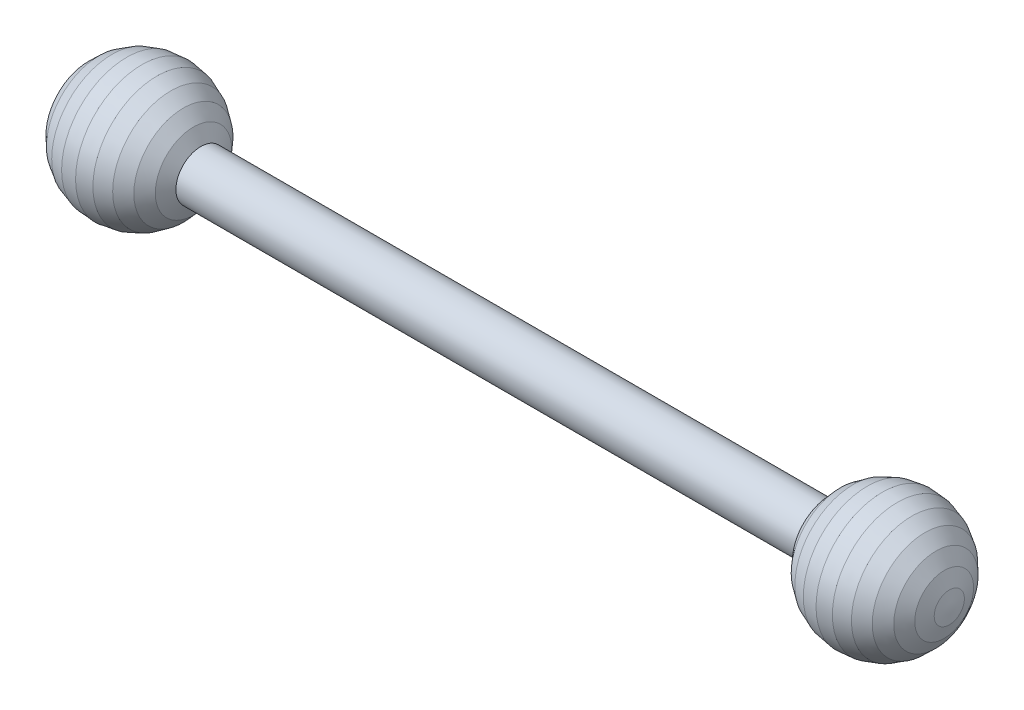
SolidWorks part; units mm, degrees
ref_plane "Front Plane" through (0, 0, 0) normal (0, 0, 1) x (1, 0, 0)
ref_plane "Top Plane" through (0, 0, 0) normal (0, 1, 0) x (1, 0, 0)
ref_plane "Right Plane" through (0, 0, 0) normal (1, 0, 0) x (0, 0, -1)
sketch "Pushrod Sketch" plane through (0, 0, 0) normal (0, 0, 1) x (1, 0, 0)
  line L0 (-1000, 0) -> (1000, 0) construction
  line L1 (-4, 0) -> (-3.8949, 0.911)
  line L2 (-3.8949, 0.911) -> (-3.585, 1.7741)
  line L3 (-3.585, 1.7741) -> (-3.0868, 2.544)
  line L4 (-3.0868, 2.544) -> (-2.4263, 3.1801)
  line L5 (-2.4263, 3.1801) -> (-1.6382, 3.6491)
  line L6 (-1.6382, 3.6491) -> (-0.7641, 3.9263)
  line L7 (-0.7641, 3.9263) -> (0.1502, 3.9972)
  line L8 (0.1502, 3.9972) -> (1.0566, 3.8579)
  line L9 (1.0566, 3.8579) -> (1.9075, 3.5159)
  line L10 (1.9075, 3.5159) -> (2.6581, 2.989)
  line L11 (2.6581, 2.989) -> (3.269, 2.3051)
  line L12 (3.269, 2.3051) -> (3.7081, 1.5)
  line L13 (3.7081, 1.5) -> (41.2725, 1.5)
  line L14 (41.2725, 1.5) -> (41.7115, 2.3051)
  line L15 (41.7115, 2.3051) -> (42.3224, 2.989)
  line L16 (42.3224, 2.989) -> (43.073, 3.5159)
  line L17 (43.073, 3.5159) -> (43.9239, 3.8579)
  line L18 (43.9239, 3.8579) -> (44.8303, 3.9972)
  line L19 (44.8303, 3.9972) -> (45.7446, 3.9263)
  line L20 (45.7446, 3.9263) -> (46.6188, 3.6491)
  line L21 (46.6188, 3.6491) -> (47.4068, 3.1801)
  line L22 (47.4068, 3.1801) -> (48.0673, 2.544)
  line L23 (48.0673, 2.544) -> (48.5656, 1.7741)
  line L24 (48.5656, 1.7741) -> (48.8754, 0.911)
  line L25 (48.8754, 0.911) -> (48.9806, 0)
  line L26 (48.9806, 0) -> (-4, 0)
revolve "Pushrod" add sketch "Pushrod Sketch" angle 360 about L0
ref_axis "Engine Axis" through (51.6296, 0, 0) along (-1, 0, 0)
sketch "End Points" plane through (0, 0, 0) normal (0, 0, 1) x (1, 0, 0)
  point P0 (0, 0)
  point P1 (44.9806, 0)
